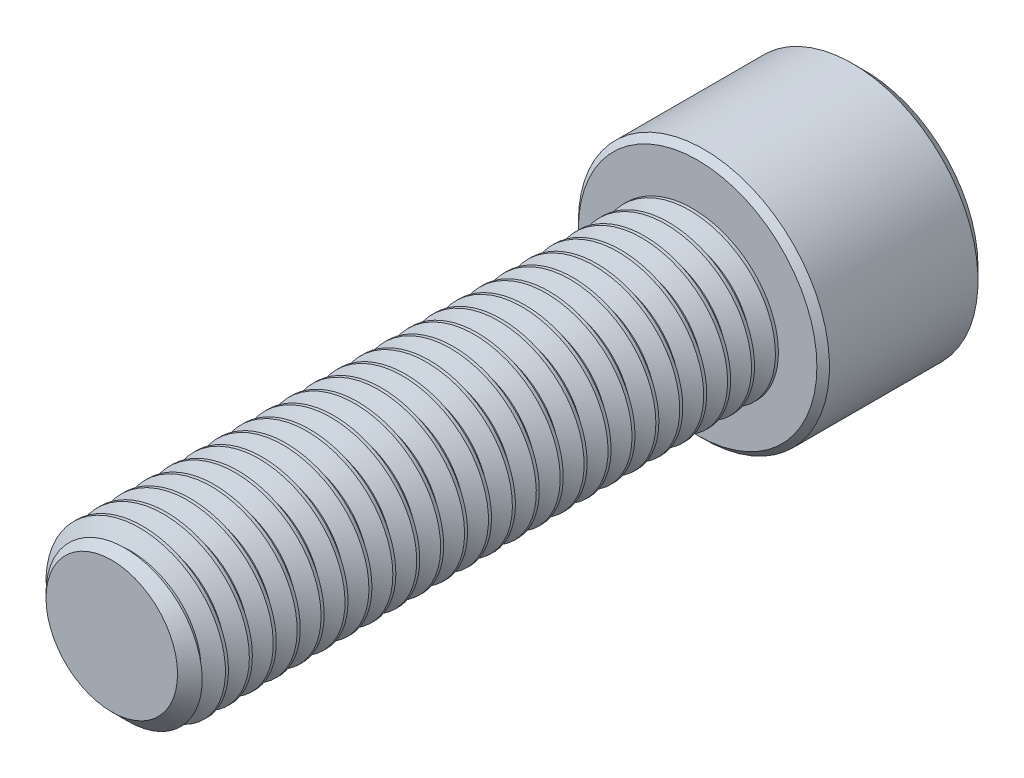
SolidWorks part; units mm, degrees
ref_plane "Front Plane" through (0, 0, 0) normal (0, 0, 1) x (1, 0, 0)
ref_plane "Top Plane" through (0, 0, 0) normal (0, 1, 0) x (1, 0, 0)
ref_plane "Right Plane" through (0, 0, 0) normal (1, 0, 0) x (0, 0, -1)
sketch "Sketch0" plane through (0, 0, 0) normal (1, 0, 0) x (0, 0, -1)
  line L0 (0, 0) -> (22.225, 0) construction
  point P2 (28.575, 0)
  point P4 (0, 0)
  dimension "D1" = 22.225
  dimension "D2" = 6.35
  dimension "Min Thread" = 0
sketch "Sketch1" plane through (0, 0, 0) normal (0, 0, 1) x (1, 0, 0)
  circle A0 centre (0, 0) radius 3.175
  dimension "OD" = 6.35
extrude "Extrude1" add sketch "Sketch1" against normal blind 22.225
sketch "Sketch2" plane through (0, 0, 0) normal (0, 0, 1) x (1, 0, 0)
  circle A0 centre (0, 0) radius 3.175 construction
  circle A1 centre (0, 0) radius 3.175
curve "Helix/Spiral1" pitch 0.9071 height 23.1321 turns 25.5 parameters "pitch"=0.9071
chamfer "Chamfer3" distance 0.6804 angle 45 1 edges at (3.175, 0, 0)
sketch "Sketch3" plane through (0, 0, 0) normal (1, 0, 0) x (0, 0, -1)
  line L0 (-0.7937, 3.175) -> (-0.4536, 2.5858)
  line L1 (-0.4536, 2.5858) -> (-0.3402, 2.5858)
  line L2 (-0.3402, 2.5858) -> (0, 3.175)
  line L3 (-0.7937, 3.175) -> (0, 3.175)
  line L4 (-0.3969, 3.175) -> (-0.3969, 2.5858) construction
  line L5 (-0.6237, 2.8804) -> (-0.1701, 2.8804) construction
  line L6 (0, 3.175) -> (0, -3.175) construction
  dimension "D1" = 0.1134
  dimension "D2" = 0.4536
  dimension "D3" = 60
sweep "Cut-Sweep1" cut profiles "Sketch3" path "Helix/Spiral1"
sketch "Sketch5" plane through (0, 0, 0) normal (1, 0, 0) x (0, 0, -1)
  line L0 (22.225, -2.2654) -> (22.225, 2.5962) construction
  line L1 (22.225, 3.175) -> (0, 3.175)
  line L2 (22.225, 3.175) -> (22.225, 0)
  line L3 (22.225, 0) -> (-1.1556, 0)
  line L4 (0, 0) -> (22.225, 0) construction
  line L5 (0, 3.175) -> (-1.1556, 0)
  line L6 (0, 0) -> (24.765, 0) construction
  dimension "D1" = 70
  dimension "D3" = 2.54
revolve "partially thread" [suppressed] add sketch "Sketch5" angle 360 about L6
sketch "Sketch6" plane through (0, 0, -22.225) normal (0, 0, -1) x (-1, 0, 0)
  circle A0 centre (0, 0) radius 4.7625
  dimension "head dia" = 9.525
extrude "Extrude2" add sketch "Sketch6" along normal blind 6.35
sketch "Sketch7" plane through (0, 0, -28.575) normal (0, 0, -1) x (-1, 0, 0)
  line L1 (0, 2.7496) -> (-2.3813, 1.3748)
  line L2 (-2.3813, 1.3748) -> (-2.3813, -1.3748)
  line L3 (-2.3813, -1.3748) -> (0, -2.7496)
  line L4 (0, -2.7496) -> (2.3813, -1.3748)
  line L5 (2.3813, -1.3748) -> (2.3813, 1.3748)
  line L6 (2.3813, 1.3748) -> (0, 2.7496)
  circle A0 centre (0, 0) radius 2.3813 construction
  dimension "hex dia" = 4.7625
extrude "Cut-Extrude1" cut sketch "Sketch7" against normal blind 3.5719
sketch "Sketch8" plane through (0, 0, -28.575) normal (0, 0, -1) x (-1, 0, 0)
  circle A0 centre (0, 0) radius 2.7496
extrude "Cut-Extrude2" cut sketch "Sketch8" against normal through all draft 45
chamfer "Chamfer1" distance 0.4763 angle 45 1 edges at (-4.7625, 0, -28.575)
chamfer "Chamfer2" distance 0.2381 angle 45 1 edges at (-4.7625, 0, -22.225)
sketch "Sketch9" plane through (0, 0, 0) normal (1, 0, 0) x (0, 0, -1)
  line L0 (0, 3.175) -> (0, -3.175) construction
  line L1 (2.2679, 3.175) -> (2.2679, -3.175) construction
  line L2 (28.575, 4.7625) -> (28.575, -4.7625) construction
  line L3 (22.225, 4.7625) -> (22.225, -4.7625) construction
  line L4 (22.225, 4.5244) -> (22.225, -4.5244) construction
  line L5 (28.575, -4.2863) -> (28.575, 4.2863) construction
  line L6 (22.225, -4.7625) -> (22.225, 4.7625) construction
  line L7 (0, 2.4946) -> (0, -2.4946) construction
  line L8 (-0.7937, 3.175) -> (0, 3.175) construction
  line L9 (2.2679, 0) -> (0, 0) construction
  dimension "D1" = 2.2679
equation "\"D3@Helix/Spiral1\" = \"screw length@Extrude1\"+\"pitch@Helix/Spiral1\""
equation "\"D1@Sketch3\" = \"pitch@Helix/Spiral1\"*.125"
equation "\"D2@Sketch3\" = \"pitch@Helix/Spiral1\"*.5"
equation "\"D1@Cut-Extrude1\" = \"hex dia@Sketch7\"*.75"
equation "\"D1@Chamfer1\" = \"head dia@Sketch6\"*.05"
equation "\"D1@Sketch9\" = \"pitch@Helix/Spiral1\"*2.50"
equation "\"D1@Chamfer2\" = \"D1@Chamfer1\"/2"
equation "\"D1@Chamfer3\" = \"pitch@Helix/Spiral1\"*.750"
equation "\"D1@Sketch0\" = \"screw length@Extrude1\""
equation "\"D2@Sketch0\" = \"head depth@Extrude2\""
